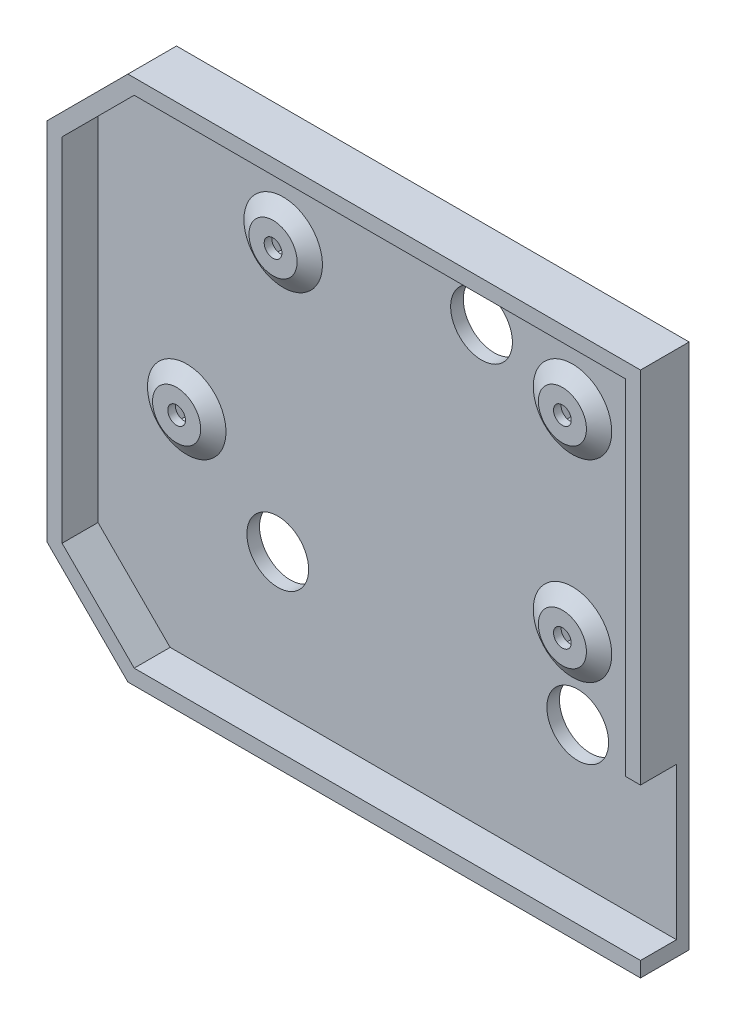
SolidWorks part; units mm, degrees
ref_plane "Plan de face" through (0, 0, 0) normal (0, 0, 1) x (1, 0, 0)
ref_plane "Plan de dessus" through (0, 0, 0) normal (0, 1, 0) x (1, 0, 0)
ref_plane "Plan de droite" through (0, 0, 0) normal (1, 0, 0) x (0, 0, -1)
sketch "Esquisse1" plane through (0, 0, 0) normal (0, 0, 1) x (1, 0, 0)
  line L0 (0, -85) -> (16, -101)
  line L4 (117.25, 3) -> (117.25, -101)
  line L5 (16, 3) -> (0, -13)
  line L7 (117.25, 3) -> (16, 3)
  line L8 (0, -13) -> (0, -85)
  line L9 (16, -101) -> (117.25, -101)
  dimension "D1" = 104
  dimension "D2" = 117.25
  dimension "D3" = 16
  dimension "D4" = 16
  dimension "D5" = 16
  dimension "D6" = 16
extrude "Boss.-Extru.1" add sketch "Esquisse1" along normal blind 2.5
sketch "Esquisse2" plane through (0, 0, 2.5) normal (0, 0, 1) x (1, 0, 0)
  line L0 (0, -13) -> (0, -85) construction
  line L1 (3, 0) -> (114.25, 0) construction
  line L2 (3, 0) -> (3, -98) construction
  line L3 (3, -98) -> (114.25, -98) construction
  line L4 (114.25, 0) -> (114.25, -98) construction
  line L5 (16, -101) -> (117.25, -101) construction
  line L6 (117.25, -101) -> (117.25, 3) construction
  line L7 (117.25, 3) -> (16, 3) construction
  line L9 (3, -83.7574) -> (17.2426, -98)
  line L10 (0, -85) -> (16, -101) construction
  line L11 (3, -14.2426) -> (17.2426, 0)
  line L12 (16, 3) -> (0, -13) construction
  line L13 (114.25, 0) -> (17.2426, 0)
  line L14 (3, -14.2426) -> (3, -83.7574)
  line L15 (17.2426, -98) -> (114.25, -98)
  line L16 (117.25, 3) -> (117.25, -101) construction
  line L17 (117.25, -101) -> (16, -101)
  line L18 (16, -101) -> (0, -85)
  line L19 (0, -85) -> (0, -13)
  line L20 (0, -13) -> (16, 3)
  line L21 (16, 3) -> (117.25, 3)
  line L30 (117.25, -2.5) -> (117.25, 3)
  line L31 (114.25, -98) -> (117.25, -98)
  line L32 (117.25, -98) -> (117.25, -101)
  line L33 (114.25, 0) -> (114.25, -68)
  line L34 (114.25, -68) -> (117.25, -68)
  line L35 (117.25, -68) -> (117.25, -2.5)
  point P24 (115.75, -98)
  dimension "D1" = 3
  dimension "D2" = 3
  dimension "D3" = 3
  dimension "D4" = 3
  dimension "D5" = 3
  dimension "D6" = 3
  dimension "D7" = 30
extrude "Boss.-Extru.2" add sketch "Esquisse2" along normal blind 7.1
sketch "Esquisse3" plane through (0, 0, 2.5) normal (0, 0, 1) x (1, 0, 0)
  line L0 (117.25, -98) -> (17.2426, -98) construction
  line L1 (17.2426, 0) -> (114.25, 0) construction
  line L2 (114.25, 0) -> (114.25, -68) construction
  line L3 (3, -83.7574) -> (3, -14.2426) construction
  circle A0 centre (97.75, -71) radius 6.1
  circle A1 centre (78.75, -12) radius 6.1
  circle A2 centre (38.5, -71) radius 6.1
  dimension "D1" = 27
  dimension "D2" = 27
  dimension "D3" = 12
  dimension "D4" = 16.5
  dimension "D5" = 35.5
  dimension "D6" = 35.5
extrude "Enlèv. mat.-Extru.1" cut sketch "Esquisse3" against normal blind 10
sketch "Esquisse4" plane through (0, 0, 2.5) normal (0, 0, 1) x (1, 0, 0)
  line L0 (114.25, 0) -> (114.25, -68) construction
  line L1 (17.2426, 0) -> (114.25, 0) construction
  point P0 (39.57, -17.53)
  point P1 (20.52, -55.63)
  point P2 (96.72, -55.63)
  point P3 (96.72, -17.53)
  dimension "D1" = 17.53
  dimension "D2" = 17.53
  dimension "D3" = 38.1
  dimension "D4" = 57.15
  dimension "D5" = 76.2
ref_axis "Axe1" through (96.72, -55.63, 2.5) along (0, 0, 1)
ref_axis "Axe2" through (20.52, -55.63, 2.5) along (0, 0, 1)
ref_axis "Axe3" through (39.57, -17.53, 2.5) along (0, 0, 1)
ref_axis "Axe4" through (96.72, -17.53, 2.5) along (0, 0, 1)
ref_plane "Plan1" through (0, -55.63, 0) normal (0, -1, 0) x (-1, 0, 0)
ref_plane "Plan2" through (0, -17.53, 0) normal (0, 1, 0) x (1, 0, 0)
sketch "Esquisse9" plane through (0, -55.63, 0) normal (0, -1, 0) x (-1, 0, 0)
  line L0 (-94.97, -2.5) -> (-88.97, -2.5)
  line L1 (-88.97, -2.5) -> (-91.97, -4.5)
  line L2 (-91.97, -4.5) -> (-94.97, -4.5)
  line L3 (-94.97, -4.5) -> (-94.97, -2.5)
  line L4 (-96.72, -2.5) -> (-96.72, -52.1725) construction
  point P0 (-98.5795, 0)
  dimension "D1" = 2
  dimension "D2" = 1.75
  dimension "D3" = 3
  dimension "D4" = 6
ref_point "Point1"
ref_point "Point2"
ref_point "Point3"
ref_point "Point4"
revolve "Révolution1" add sketch "Esquisse9" angle 360 about axis through (96.72, -55.63, 2.5) along (0, 0, 1)
sketch "Esquisse11" plane through (0, -55.63, 0) normal (0, -1, 0) x (-1, 0, 0)
  line L0 (-22.27, -2.5) -> (-28.27, -2.5)
  line L1 (-28.27, -2.5) -> (-25.27, -4.5)
  line L2 (-25.27, -4.5) -> (-22.27, -4.5)
  line L3 (-22.27, -4.5) -> (-22.27, -2.5)
  line L4 (-20.52, -2.5) -> (-20.52, -52.1725) construction
  dimension "D1" = 1.75
  dimension "D2" = 3
  dimension "D3" = 6
  dimension "D4" = 2
revolve "Révolution2" add sketch "Esquisse11" angle 360 about axis through (20.52, -55.63, 2.5) along (0, 0, 1)
sketch "Esquisse12" plane through (0, -17.53, 0) normal (0, 1, 0) x (1, 0, 0)
  line L0 (94.97, -2.5) -> (88.97, -2.5)
  line L1 (88.97, -2.5) -> (91.97, -4.5)
  line L2 (91.97, -4.5) -> (94.97, -4.5)
  line L3 (94.97, -4.5) -> (94.97, -2.5)
  line L4 (96.72, -2.5) -> (96.72, -52.1725) construction
  dimension "D1" = 1.75
  dimension "D2" = 2
  dimension "D3" = 3
  dimension "D4" = 6
revolve "Révolution3" add sketch "Esquisse12" angle 360 about axis through (96.72, -17.53, 2.5) along (0, 0, 1)
sketch "Esquisse13" plane through (0, -17.53, 0) normal (0, 1, 0) x (1, 0, 0)
  line L0 (41.32, -2.5) -> (47.32, -2.5)
  line L1 (47.32, -2.5) -> (44.32, -4.5)
  line L2 (44.32, -4.5) -> (41.32, -4.5)
  line L3 (41.32, -4.5) -> (41.32, -2.5)
  line L4 (39.57, -2.5) -> (39.57, -52.1725) construction
  dimension "D1" = 1.75
  dimension "D2" = 3
  dimension "D3" = 6
  dimension "D4" = 2
revolve "Révolution4" add sketch "Esquisse13" angle 360 about axis through (39.57, -17.53, 2.5) along (0, 0, 1)
hole_wizard "Dégagement M31" positions "Esquisse14" profile "Esquisse15" hole size "M3" standard "Ansi Metric" end condition up to next
sketch "Esquisse14" plane through (0, 0, 2.5) normal (0, 0, 1) x (1, 0, 0)
  point P0 (96.72, -55.63)
  point P3 (20.52, -55.63)
  point P6 (96.72, -17.53)
  point P9 (39.57, -17.53)
sketch "Esquisse15" plane through (96.72, -55.63, 2.5) normal (1, 0, 0) x (0, -1, 0)
  line L0 (0, 0) -> (0, 2.5)
  line L1 (0, 2.5) -> (1.8, 2.5)
  line L2 (1.8, 2.5) -> (1.8, 0)
  line L5 (1.8, 0) -> (0, 0)
  line L11 (0, -6.35) -> (0, 107.95) construction
  dimension "Diamètre du perçage jusqu'au prochain" = 3.6
  dimension "Profondeur du perçage jusqu'au prochain" = 2.5
ref_point "Point5"
ref_point "Point6"
ref_point "Point7"
ref_point "Point8"
sketch "Esquisse16" plane through (0, 0, 0) normal (0, 0, -1) x (-1, 0, 0)
  line L0 (-117.25, 3) -> (-16, 3) construction
  line L1 (-22.0788, -52.93) -> (-23.6377, -55.63)
  line L2 (-23.6377, -55.63) -> (-22.0788, -58.33)
  line L3 (-22.0788, -58.33) -> (-18.9612, -58.33)
  line L4 (-18.9612, -58.33) -> (-17.4023, -55.63)
  line L5 (-17.4023, -55.63) -> (-18.9612, -52.93)
  line L6 (-18.9612, -52.93) -> (-22.0788, -52.93)
  line L7 (-98.2788, -52.93) -> (-99.8377, -55.63)
  line L8 (-99.8377, -55.63) -> (-98.2788, -58.33)
  line L9 (-98.2788, -58.33) -> (-95.1612, -58.33)
  line L10 (-95.1612, -58.33) -> (-93.6023, -55.63)
  line L11 (-93.6023, -55.63) -> (-95.1612, -52.93)
  line L12 (-95.1612, -52.93) -> (-98.2788, -52.93)
  line L13 (-98.2788, -14.83) -> (-99.8377, -17.53)
  line L14 (-99.8377, -17.53) -> (-98.2788, -20.23)
  line L15 (-98.2788, -20.23) -> (-95.1612, -20.23)
  line L16 (-95.1612, -20.23) -> (-93.6023, -17.53)
  line L17 (-93.6023, -17.53) -> (-95.1612, -14.83)
  line L18 (-95.1612, -14.83) -> (-98.2788, -14.83)
  line L19 (-41.1288, -14.83) -> (-42.6877, -17.53)
  line L20 (-42.6877, -17.53) -> (-41.1288, -20.23)
  line L21 (-41.1288, -20.23) -> (-38.0112, -20.23)
  line L22 (-38.0112, -20.23) -> (-36.4523, -17.53)
  line L23 (-36.4523, -17.53) -> (-38.0112, -14.83)
  line L24 (-38.0112, -14.83) -> (-41.1288, -14.83)
  circle A0 centre (-20.52, -55.63) radius 2.7 construction
  circle A1 centre (-96.72, -55.63) radius 2.7 construction
  circle A2 centre (-96.72, -17.53) radius 2.7 construction
  circle A3 centre (-39.57, -17.53) radius 2.7 construction
  dimension "D1" = 5.4
  dimension "D2" = 5.4
  dimension "D3" = 5.4
  dimension "D4" = 5.4
extrude "Enlèv. mat.-Extru.2" cut sketch "Esquisse16" against normal blind 3
